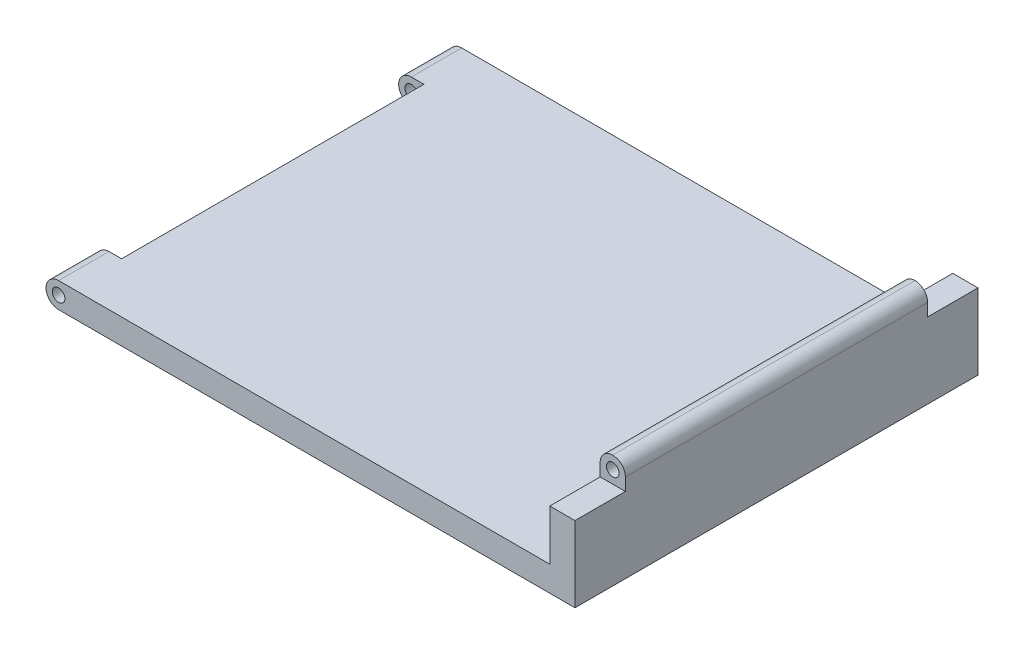
SolidWorks part; units mm, degrees
ref_plane "Front Plane" through (0, 0, 0) normal (0, 0, 1) x (1, 0, 0)
ref_plane "Top Plane" through (0, 0, 0) normal (0, 1, 0) x (1, 0, 0)
ref_plane "Right Plane" through (0, 0, 0) normal (1, 0, 0) x (0, 0, -1)
sketch "Sketch1" plane through (0, 0, 0) normal (0, 0, 1) x (1, 0, 0)
  line L0 (0, 0) -> (100, 0)
  line L1 (100, 0) -> (100, 20)
  line L2 (100, 20) -> (95, 20)
  line L3 (95, 20) -> (95, 5)
  line L4 (95, 5) -> (0, 5)
  line L5 (0, 5) -> (0, 0)
  dimension "D1" = 100
  dimension "D2" = 5
  dimension "D3" = 5
  dimension "D4" = 20
extrude "Boss-Extrude1" add sketch "Sketch1" along normal mid plane 80
sketch "Sketch2" plane through (0, 0, 0) normal (0, 0, 1) x (1, 0, 0)
  line L0 (0, 5) -> (-2.5, 5)
  line L1 (-2.5, 0) -> (0, 0)
  line L2 (0, 0) -> (0, 5)
  arc A0 (-2.5, 5) -> (-2.5, 0) centre (-2.5, 2.5) ccw
  circle A1 centre (-2.5, 2.5) radius 1.25
  dimension "D1" = 2.5
  dimension "D2" = 2.5
extrude "Boss-Extrude2" add sketch "Sketch2" along normal blind 10 from offset 30
mirror "Mirror2" about plane through (0, 0, 0) normal (0, 0, 1) of "Boss-Extrude2"
sketch "Sketch3" plane through (0, 0, 0) normal (0, 0, 1) x (1, 0, 0)
  line L0 (100, 0) -> (100, 20) construction
  line L1 (95, 20) -> (100, 20)
  line L2 (95, 20) -> (95, 15)
  line L3 (95, 15) -> (100, 15)
  line L4 (100, 20) -> (100, 15)
  dimension "D1" = 5
extrude "Cut-Extrude1" cut sketch "Sketch3" against normal blind 10 from offset 30 offset against normal yes
mirror "Mirror3" about plane through (0, 0, 0) normal (0, 0, 1) of "Cut-Extrude1"
sketch "Sketch4" plane through (0, 0, 0) normal (0, 0, 1) x (1, 0, 0)
  line L0 (100, 20) -> (95, 20) construction
  circle A0 centre (97.5, 17.5) radius 1.25
  point P5 (97.5, 20)
  dimension "D1" = 2.5
  dimension "D2" = 2.5
extrude "Cut-Extrude2" cut sketch "Sketch4" against normal through all both and the other way through all
fillet "Fillet1" radius 2.5 2 edges at (95, 20, 0) (100, 20, 0)
